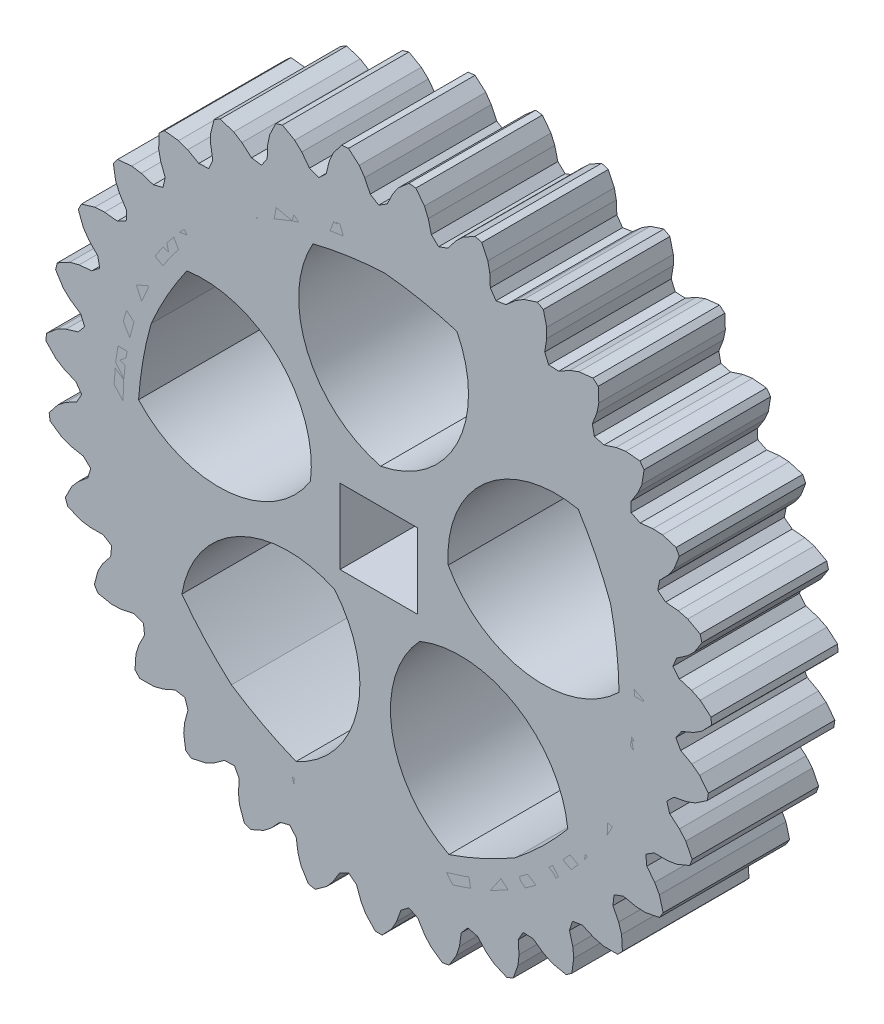
SolidWorks part; units mm, degrees
ref_plane "Front Plane" through (0, 0, 0) normal (0, 0, 1) x (1, 0, 0)
ref_plane "Top Plane" through (0, 0, 0) normal (0, 1, 0) x (1, 0, 0)
ref_plane "Right Plane" through (0, 0, 0) normal (1, 0, 0) x (0, 0, -1)
sketch "Sketch1" plane through (0, 0, 0) normal (0, 0, 1) x (1, 0, 0)
  line L1 (3.675, -3.55) -> (-3.675, -3.55)
  line L2 (3.675, -3.55) -> (3.675, 3.55)
  line L3 (3.675, 3.55) -> (-3.675, 3.55)
  line L4 (-3.675, -3.55) -> (-3.675, 3.55)
  circle A0 centre (0, 0) radius 31.574
  point P3 (0, 3.55)
  point P8 (0, 0)
  point P9 (-3.675, 0)
  dimension "D1" = 63.148
  dimension "D2" = 7.35
  dimension "D3" = 7.1
extrude "Boss-Extrude1" add sketch "Sketch1" along normal blind 12
sketch "Sketch2" plane through (0, 0, 0) normal (0, 0, 1) x (1, 0, 0)
  line L0 (0, 0) -> (0, 32.8121) construction
  line L1 (0, 28.214) -> (-0.8069, 28.7123)
  line L2 (-0.8069, 28.7123) -> (-1.33, 29.8022)
  line L3 (-1.33, 29.8022) -> (-1.8557, 30.5578)
  line L4 (-1.8557, 30.5578) -> (-2.8665, 31.4436)
  line L5 (-2.8665, 31.4436) -> (-1.8557, 32.2161)
  line L6 (-1.8557, 32.2161) -> (0, 32.8121)
  line L7 (1.8557, 32.2161) -> (0, 32.8121)
  line L8 (2.8665, 31.4436) -> (1.8557, 32.2161)
  line L9 (1.8557, 30.5578) -> (2.8665, 31.4436)
  line L10 (1.33, 29.8022) -> (1.8557, 30.5578)
  line L11 (0.8069, 28.7123) -> (1.33, 29.8022)
  line L12 (0, 28.214) -> (0.8069, 28.7123)
  circle A22 centre (0, 0) radius 31.574 construction
  dimension "D5" = 0.5258
  dimension "D6" = 0.7556
  dimension "D9" = 0.5959
  dimension "D1" = 0.8069
  dimension "D2" = 0.4984
  dimension "D3" = 0.5231
  dimension "D4" = 1.0898
  dimension "D7" = 0.8858
  dimension "D8" = 1.8557
  dimension "D10" = 1.0107
  dimension "D11" = 0.7725
  dimension "D12" = 1.0107
extrude "Cut-Extrude1" cut sketch "Sketch2" along normal through all
pattern_circular "CirPattern1" count 31 over 360 about axis through (0, 0, 12) along (0, 0, -1) of "Cut-Extrude1"
sketch "Sketch3" plane through (0, 0, 0) normal (0, 0, 1) x (1, 0, 0)
  circle A0 centre (0, 0) radius 29.75
  dimension "D1" = 59.5
sketch "Sketch4" plane through (0, 0, 0) normal (0, 0, 1) x (1, 0, 0)
  line L0 (0, 0) -> (0.6245, 22.9095) construction
  arc A0 (0.1872, 6.8675) -> (-6.2369, 21.9201) centre (2.6671, 16.823) cw
  arc A1 (0.6245, 22.9095) -> (-6.2369, 21.9201) centre (2.0438, -11.2177) ccw
  arc A2 (0.6245, 22.9095) -> (7.4217, 21.5478) centre (-2.6519, -11.0897) cw
  arc A3 (0.1872, 6.8675) -> (7.4217, 21.5478) centre (-1.7467, 16.9433) ccw
extrude "Cut-Extrude2" cut sketch "Sketch4" along normal through all both
sketch "Sketch5" plane through (0, 0, 0) normal (0, 0, 1) x (1, 0, 0)
  circle A0 centre (0, 0) radius 25.1098
  circle A1 centre (0, 0) radius 24.2496
extrude "Boss-Extrude2" add sketch "Sketch5" along normal through all separate body
pattern_circular "CirPattern2" count 5 over 360 about axis through (0, 0, 12) along (0, 0, -1) of "Cut-Extrude2" reverse direction yes
chamfer "Chamfer1" distance 1.5 distance2 0.5 4 edges at (-3.675, 0, 0) (0, -3.55, 0) (3.675, 0, 0) (0, 3.55, 0) first distance on face at (-3.675, 0, 6) first distance on face at (0, -3.55, 6) first distance on face at (3.675, 0, 6) first distance on face at (0, 3.55, 6)
